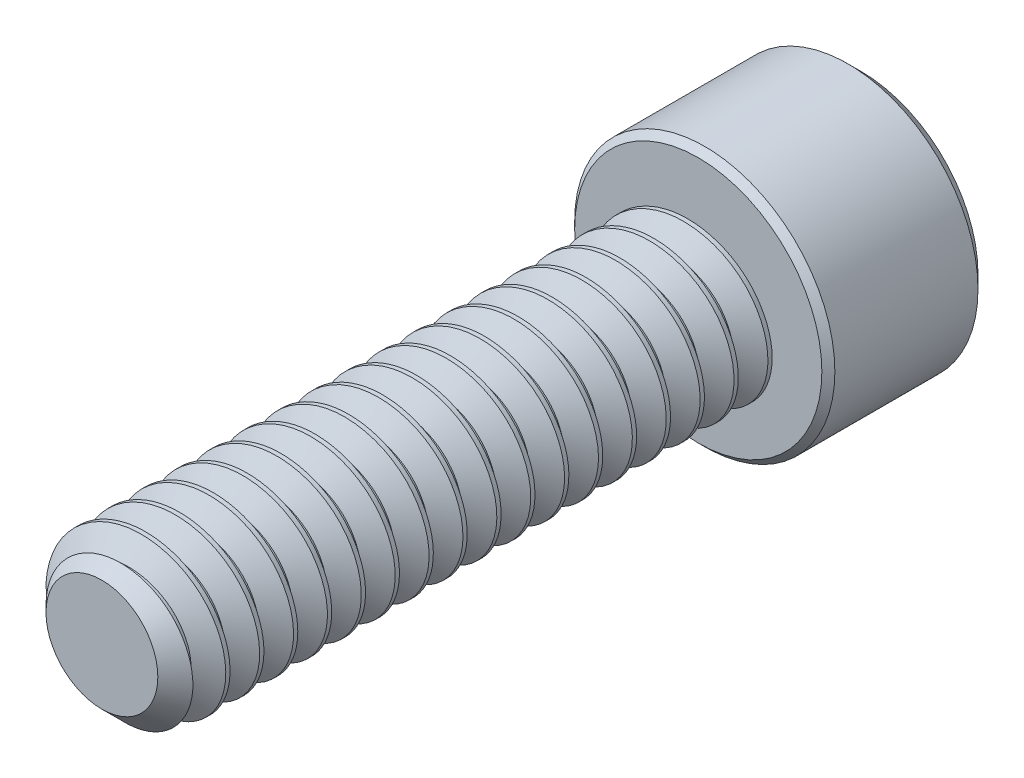
SolidWorks part; units mm, degrees
ref_plane "Front Plane" through (0, 0, 0) normal (0, 0, 1) x (1, 0, 0)
ref_plane "Top Plane" through (0, 0, 0) normal (0, 1, 0) x (1, 0, 0)
ref_plane "Right Plane" through (0, 0, 0) normal (1, 0, 0) x (0, 0, -1)
sketch "Sketch0" plane through (0, 0, 0) normal (1, 0, 0) x (0, 0, -1)
  line L0 (0, 0) -> (5.588, 0) construction
  point P2 (7.112, 0)
  point P4 (0, 0)
  dimension "D1" = 5.588
  dimension "D2" = 1.524
  dimension "Min Thread" = 0
sketch "Sketch1" plane through (0, 0, 0) normal (0, 0, 1) x (1, 0, 0)
  circle A0 centre (0, 0) radius 0.762
  dimension "OD" = 1.524
extrude "Extrude1" add sketch "Sketch1" against normal blind 5.588
sketch "Sketch2" plane through (0, 0, 0) normal (0, 0, 1) x (1, 0, 0)
  circle A0 centre (0, 0) radius 0.762 construction
  circle A1 centre (0, 0) radius 0.762
curve "Helix/Spiral1" pitch 0.3175 height 6.6675 radius 0.762 centre (0, 0, 0) axis (0, 0, -1) start towards (0, 1, 0) parameters "pitch"=0.3175
chamfer "Chamfer3" distance 0.2381 angle 45 1 edges at (0.762, 0, 0)
sketch "Sketch3" plane through (0, 0, 0) normal (1, 0, 0) x (0, 0, -1)
  line L0 (-0.2778, 0.762) -> (-0.1587, 0.5558)
  line L1 (-0.1587, 0.5558) -> (-0.1191, 0.5558)
  line L2 (-0.1191, 0.5558) -> (0, 0.762)
  line L3 (-0.2778, 0.762) -> (0, 0.762)
  line L4 (-0.1389, 0.762) -> (-0.1389, 0.5558) construction
  line L5 (-0.2183, 0.6589) -> (-0.0595, 0.6589) construction
  line L6 (0, 0.762) -> (0, -0.762) construction
  dimension "D1" = 0.0397
  dimension "D2" = 0.1588
  dimension "D3" = 60
sweep "Cut-Sweep1" cut profiles "Sketch3" path "Helix/Spiral1" align with end faces yes
sketch "Sketch5" plane through (0, 0, 0) normal (1, 0, 0) x (0, 0, -1)
  line L0 (5.588, -0.7515) -> (5.588, 0.4511) construction
  line L1 (5.588, 0.762) -> (0, 0.762)
  line L2 (5.588, 0.762) -> (5.588, 0)
  line L3 (5.588, 0) -> (-0.2773, 0)
  line L4 (0, 0) -> (5.588, 0) construction
  line L5 (0, 0.762) -> (-0.2773, 0)
  line L6 (0, 0) -> (8.128, 0) construction
  dimension "D1" = 70
  dimension "D3" = 2.54
revolve "partially thread" [suppressed] add sketch "Sketch5" angle 360 about L6
sketch "Sketch6" plane through (0, 0, -5.588) normal (0, 0, -1) x (-1, 0, 0)
  circle A0 centre (0, 0) radius 1.2192
  dimension "head dia" = 2.4384
extrude "Extrude2" add sketch "Sketch6" along normal blind 1.524
sketch "Sketch7" plane through (0, 0, -7.112) normal (0, 0, -1) x (-1, 0, 0)
  line L1 (0, 0.7332) -> (-0.635, 0.3666)
  line L2 (-0.635, 0.3666) -> (-0.635, -0.3666)
  line L3 (-0.635, -0.3666) -> (0, -0.7332)
  line L4 (0, -0.7332) -> (0.635, -0.3666)
  line L5 (0.635, -0.3666) -> (0.635, 0.3666)
  line L6 (0.635, 0.3666) -> (0, 0.7332)
  circle A0 centre (0, 0) radius 0.635 construction
  dimension "hex dia" = 1.27
extrude "Cut-Extrude1" cut sketch "Sketch7" against normal blind 0.9525
sketch "Sketch8" plane through (0, 0, -7.112) normal (0, 0, -1) x (-1, 0, 0)
  circle A0 centre (0, 0) radius 0.7332
extrude "Cut-Extrude2" cut sketch "Sketch8" against normal through all draft 45
chamfer "Chamfer1" distance 0.1219 angle 45 1 edges at (-1.2192, 0, -7.112)
chamfer "Chamfer2" distance 0.061 angle 45 1 edges at (-1.2192, 0, -5.588)
sketch "Sketch9" plane through (0, 0, 0) normal (1, 0, 0) x (0, 0, -1)
  line L0 (0, 0.762) -> (0, -0.762) construction
  line L1 (1.4287, 0.762) -> (1.4288, -0.762) construction
  line L2 (7.112, 1.2192) -> (7.112, -1.2192) construction
  line L3 (5.588, 1.2192) -> (5.588, -1.2192) construction
  line L4 (5.588, 1.1582) -> (5.588, -1.1582) construction
  line L5 (7.112, -1.0973) -> (7.112, 1.0973) construction
  line L6 (5.588, -1.2192) -> (5.588, 1.2192) construction
  line L7 (0, 0.5239) -> (0, -0.5239) construction
  line L8 (-0.2778, 0.762) -> (0, 0.762) construction
  line L9 (1.4287, 0) -> (0, 0) construction
  dimension "D1" = 1.4287
equation "\"D3@Helix/Spiral1\" = \"screw length@Extrude1\"+\"pitch@Helix/Spiral1\""
equation "\"D1@Sketch3\" = \"pitch@Helix/Spiral1\"*.125"
equation "\"D2@Sketch3\" = \"pitch@Helix/Spiral1\"*.5"
equation "\"D1@Cut-Extrude1\" = \"hex dia@Sketch7\"*.75"
equation "\"D1@Chamfer1\" = \"head dia@Sketch6\"*.05"
equation "\"D1@Sketch9\" = \"pitch@Helix/Spiral1\"*4.50"
equation "\"D1@Chamfer2\" = \"D1@Chamfer1\"/2"
equation "\"D1@Chamfer3\" = \"pitch@Helix/Spiral1\"*.750"
equation "\"D2@Sketch0\" = \"head depth@Extrude2\""
